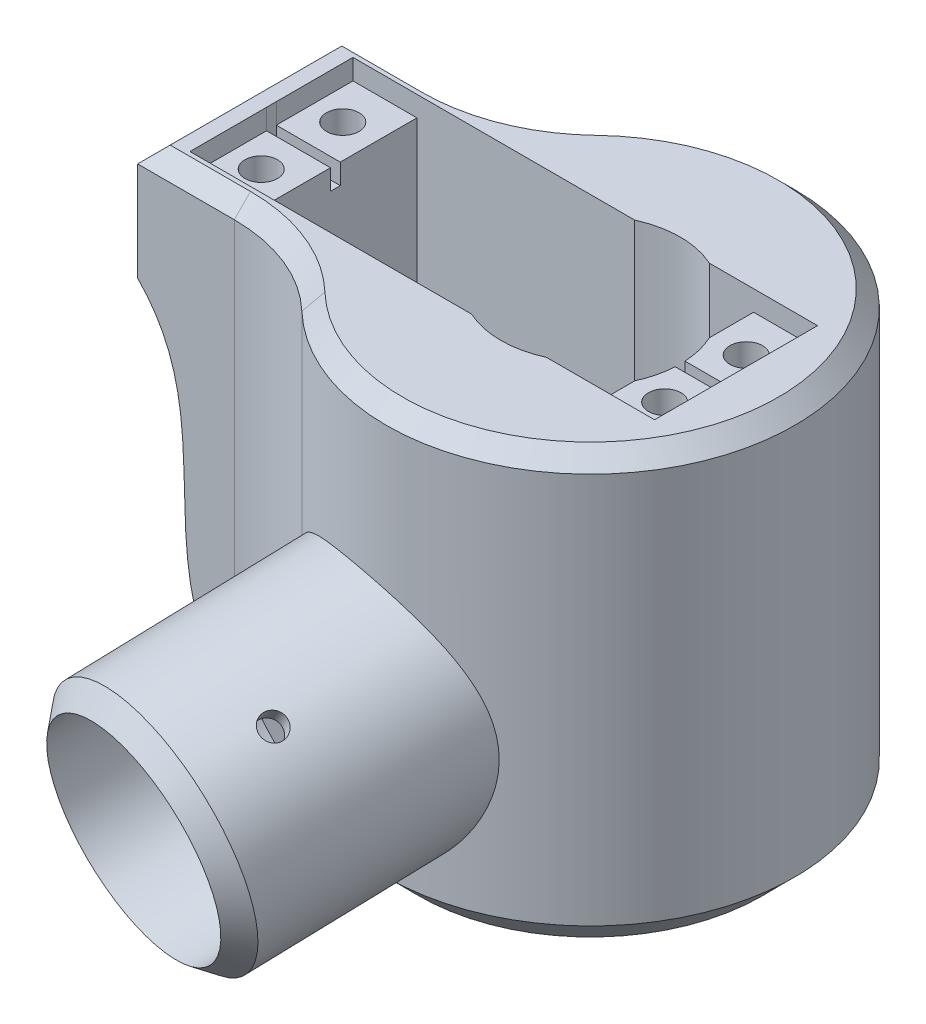
SolidWorks part; units mm, degrees
material "Melamine resin"
ref_plane "Front Plane" through (0, 0, 0) normal (0, 0, 1) x (1, 0, 0)
ref_plane "Top Plane" through (0, 0, 0) normal (0, 1, 0) x (1, 0, 0)
ref_plane "Right Plane" through (0, 0, 0) normal (1, 0, 0) x (0, 0, -1)
sketch "Sketch1" plane through (0, 0, 0) normal (0, 1, 0) x (1, 0, 0)
  line L3 (-34.0477, -12.5248) -> (-22.1886, -12.5248)
  line L4 (-34.0477, -12.5248) -> (-34.0477, 12.5248)
  line L5 (-34.0477, 12.5248) -> (-22.1886, 12.5248)
  arc A3 (-8.3278, -18.0914) -> (-22.1886, -12.5248) centre (-22.1886, -32.5646) ccw
  arc A4 (-22.1886, 12.5248) -> (-8.3278, 18.0914) centre (-22.1886, 32.5646) ccw
  arc A5 (-8.3278, -18.0914) -> (-8.3278, 18.0914) centre (8.9981, 0) ccw
  dimension "D1" = 20.0397
  dimension "D2" = 25.0497
extrude "Boss-Extrude2" add sketch "Sketch1" along normal blind 54
ref_axis "Axis1" through (8.9981, 54, 0) along (0, -1, 0)
ref_point "Point1"
sketch3d "3DSketch1"
  line L0 (8.9981, 25, 0) -> (-7.5398, 5.3755, 91.6321)
  line L4 (-23.4294, -13.4798, 179.6725) -> (8.9981, 25, 0) construction
  point P2 (0, 0, 0)
  point P3 (0, 0, 0)
  point P4 (0, 0, 0)
  point P5 (0, 0, 0)
  point P6 (0, 0, 0)
ref_plane "Plane1" through (0, 25, 0) normal (0, 1, 0) x (1, 0, 0)
sketch "Sketch2" plane through (0, 25, 0) normal (0, 1, 0) x (1, 0, 0)
  point P0 (8.9981, 0)
  point P1 (0, 0)
  point P3 (8.9981, 0)
  point P4 (0, 0)
  point P5 (0, 0)
  point P6 (0, 0)
  point P7 (0, 0)
  point P8 (0, 0)
chamfer "Chamfer1" distance 2 angle 45 5 edges at (-14.7202, 54, 13.9685) (-14.7202, 54, -13.9685) (34.0477, 54, 0) (-28.1181, 54, 12.5248) (-28.1181, 54, -12.5248)
ref_plane "Plane2" through (8.9981, 25, 0) normal (-0.1738, -0.2062, 0.9629) x (0.9848, -0.0364, 0.1699)
sketch "Sketch3" plane through (8.9981, 25, 0) normal (-0.1738, -0.2062, 0.9629) x (0.9848, -0.0364, 0.1699)
  circle A0 centre (0, 0) radius 15
  point P3 (0, 0)
  point P4 (0.4724, -1.0834)
  dimension "D1" = 30
extrude "Boss-Extrude3" add sketch "Sketch3" along a picked direction on the side of the normal blind 50
sketch "Sketch5" plane through (-7.5218, -8.9257, 41.6767) normal (-0.1738, -0.2062, 0.9629) x (0.9848, -0.0373, 0.1698)
  circle A0 centre (7.9298, 24.4526) radius 12.7
  point P3 (0, 0)
  dimension "D1" = 25.4
extrude "Cut-Extrude1" cut sketch "Sketch5" against normal blind 21
chamfer "Chamfer2" distance 3 angle 45 1 edges at (0.3084, 0.0211, 45.006)
ref_plane "Plane3" through (-22.1886, 52, -12.5248) normal (-0.5664, -0.779, -0.2691) x (-0.8242, 0.5354, 0.1848)
sketch "Sketch6" plane through (-22.1886, 52, -12.5248) normal (-0.5664, -0.779, -0.2691) x (-0.8242, 0.5354, 0.1848)
  line L0 (-23.778, -63.2237) -> (-29.7998, -57.957) construction
  line L2 (-37.8434, -20.6484) -> (-17.7885, -113.6691) construction
  circle A0 centre (-29.7998, -57.957) radius 1.5
  dimension "D1" = 3
  dimension "D2" = 8
extrude "Cut-Extrude2" cut sketch "Sketch6" against normal mid plane 97
ref_point "Point2"
sketch "Sketch7" plane through (0, 0, 0) normal (0, -1, 0) x (-1, 0, 0)
  circle A0 centre (-8.9981, 0) radius 4
  dimension "D1" = 8
extrude "Cut-Extrude3" cut sketch "Sketch7" against normal blind 82
sketch "Sketch9" plane through (0, 0, 0) normal (0, -1, 0) x (1, 0, 0)
  circle A0 centre (8.9981, 0) radius 11
  dimension "D1" = 22
extrude "Cut-Extrude4" cut sketch "Sketch9" against normal blind 8
chamfer "Chamfer3" distance 2 angle 45 1 edges at (-34.0477, 54, 0)
sketch "Sketch10" plane through (0, 0, -12.5248) normal (0, 0, -1) x (-1, 0, 0)
  line L0 (22.1867, 0) -> (34.0477, 0)
  line L1 (34.0477, 0) -> (34.0477, 39.8592)
  line L2 (34.0477, 52) -> (34.0477, 0) construction
  line L3 (34.0477, 52) -> (22.1886, 52) construction
  spline S0 degree 3 poles (22.1867, 0) (33.5541, 11.2638) (23.1647, 28.9343) (34.0477, 39.8592) knots 0 0 0 0 1 1 1 1
extrude "Cut-Extrude5" cut sketch "Sketch10" against normal blind 96
sketch3d "3DSketch2"
  line L0 (8.9981, 54, 0) -> (8.9981, 0, 0) construction
  point P0 (8.9981, 25, 0)
  point P1 (8.9981, 27, 0)
  point P5 (0, 0, 0)
  point P6 (0, 0, 0)
sketch "Sketch11" plane through (0, 54, 0) normal (0, 1, 0) x (1, 0, 0)
  line L0 (25.8463, 0) -> (-43.2495, 0) construction
  line L1 (18.9981, 10.25) -> (-22.3055, 10.25)
  line L2 (18.9981, 10.25) -> (18.9981, -10.25)
  line L3 (18.9981, -10.25) -> (-22.3055, -10.25)
  line L4 (-22.3055, 10.25) -> (-22.3055, -10.25)
  line L5 (18.9981, 10.25) -> (-22.3055, -10.25) construction
  line L6 (18.9981, -10.25) -> (-22.3055, 10.25) construction
  line L7 (-29.1537, 10) -> (25.8463, 10)
  line L8 (-29.1537, 10) -> (-29.1537, -10)
  line L9 (-29.1537, -10) -> (25.8463, -10)
  line L10 (25.8463, 10) -> (25.8463, -10)
  line L11 (-29.1537, 10) -> (25.8463, -10) construction
  line L12 (-29.1537, -10) -> (25.8463, 10) construction
  line L13 (-1.6537, 0) -> (-1.6537, -13.0522) construction
  line L14 (12.1499, 0.6) -> (25.8463, 0.6)
  line L15 (12.1499, 0.6) -> (12.1499, -0.6)
  line L16 (12.1499, -0.6) -> (25.8463, -0.6)
  line L17 (25.8463, 0.6) -> (25.8463, -0.6)
  line L18 (12.1499, 0.6) -> (25.8463, -0.6) construction
  line L19 (12.1499, -0.6) -> (25.8463, 0.6) construction
  line L20 (-1.6537, -13.0522) -> (-1.6537, 13.6107) construction
  line L21 (-29.1537, 10) -> (-29.1537, -10)
  line L22 (-15.4573, 0.6) -> (-15.4573, -0.6)
  line L23 (-15.4573, -0.6) -> (-29.1537, -0.6)
  line L24 (-15.4573, 0.6) -> (-29.1537, 0.6)
  circle A0 centre (23.0963, -5) radius 2
  circle A1 centre (23.0963, 5) radius 2
  circle A2 centre (-26.4037, -5) radius 2
  circle A3 centre (-26.4037, 5) radius 2
  point P0 (7.4947, -4.5406)
  point P5 (-1.6537, 0)
  point P10 (18.9981, 0)
  circle M6 centre (8.9981, 0) radius 4
  dimension "D5" = 4
  dimension "D1" = 20.5
  dimension "D2" = 41.3036
  dimension "D3" = 55
  dimension "D4" = 1.2
  dimension "D6" = 5
  dimension "D7" = 2.75
  dimension "D8" = 10
extrude "Cut-Extrude6" cut sketch "Sketch11" against normal blind 34 contours L24 L22 L23 L4 L9 L2 L16 L14 L7 M6 | A1 | A0 | A2 | A3 | L16 L2 L14 M6 | L15 L16 L14 M6 | L16 L15 L14 M6 | L22 L24 L4 L23 region at (-2.3392, 54, 0) region at (15.9905, 54, 0) region at (-18.8814, 54, 0) region at (12.5665, 54, 0) region at (8.9256, 54, 0) region at (23.0963, 54, 5) region at (23.0963, 54, -5) region at (-26.4037, 54, 5) region at (-26.4037, 54, -5)
sketch "Sketch12" plane through (0, 54, 0) normal (0, 1, 0) x (1, 0, 0)
  line L0 (18.9981, 0) -> (-33.6264, 0) construction
  line L1 (18.9981, 10) -> (18.9981, -10) construction
  line L2 (0, 0) -> (0, -14.2019) construction
  line L3 (11.1481, 0.6) -> (26.8481, 0.6)
  line L4 (11.1481, 0.6) -> (11.1481, -0.6)
  line L5 (11.1481, -0.6) -> (26.8481, -0.6)
  line L6 (26.8481, 0.6) -> (26.8481, -0.6)
  line L7 (11.1481, 0.6) -> (26.8481, -0.6) construction
  line L8 (11.1481, -0.6) -> (26.8481, 0.6) construction
  line L9 (0, -14.2019) -> (0, 17.0976) construction
  line L10 (18.9981, 10) -> (18.9981, -10) construction
  line L11 (-22.3055, 10) -> (-22.3055, -10) construction
  line L12 (-14.4555, 0.6) -> (-30.1555, 0.6)
  line L13 (-14.4555, 0.6) -> (-14.4555, -0.6)
  line L14 (-14.4555, -0.6) -> (-30.1555, -0.6)
  line L15 (-30.1555, 0.6) -> (-30.1555, -0.6)
  line L16 (-14.4555, 0.6) -> (-30.1555, -0.6) construction
  line L17 (-14.4555, -0.6) -> (-30.1555, 0.6) construction
  point P14 (-22.3055, 0)
  dimension "D1" = 1.2
  dimension "D2" = 7.85
  dimension "D3" = 1.2
  dimension "D4" = 7.85
extrude "Cut-Extrude7" cut sketch "Sketch12" against normal blind 5
sketch "Sketch13" plane through (0, 54, 0) normal (0, 1, 0) x (1, 0, 0)
  line L0 (26.8481, -0.6) -> (26.8481, 0.6) construction
  line L1 (-30.1519, 10) -> (26.8481, 10)
  line L2 (-30.1519, 10) -> (-30.1519, -10)
  line L3 (-30.1519, -10) -> (26.8481, -10)
  line L4 (26.8481, 10) -> (26.8481, -10)
  line L5 (-30.1519, 10) -> (26.8481, -10) construction
  line L6 (-30.1519, -10) -> (26.8481, 10) construction
  line L7 (-1.6519, 0) -> (2.2395, 0) construction
  point P5 (0, 0)
  dimension "D1" = 20
  dimension "D2" = 57
extrude "Cut-Extrude8" cut sketch "Sketch13" against normal blind 2.5
sketch "Sketch14" plane through (0, 54, 0) normal (0, 1, 0) x (1, 0, 0)
  circle A0 centre (8.9981, 0) radius 11
  dimension "D1" = 22
extrude "Cut-Extrude9" cut sketch "Sketch14" against normal blind 42
chamfer "Chamfer4" distance 4 angle 45 3 edges at (-14.7193, 0, 13.9688) (-14.7193, 0, -13.9688) (34.0477, 0, 0)
